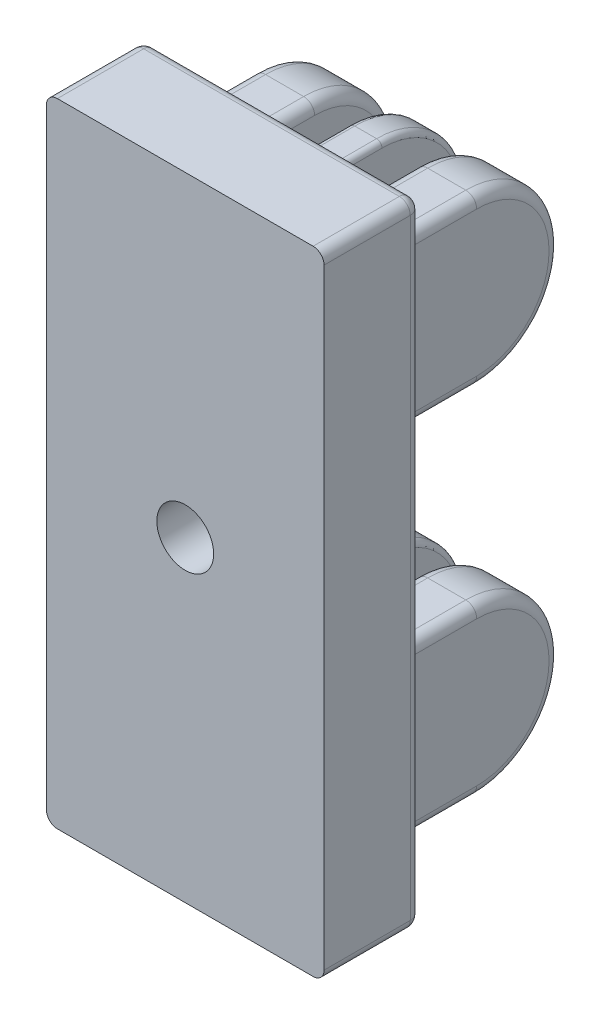
SolidWorks part; units mm, degrees
ref_plane "Front Plane" through (0, 0, 0) normal (0, 0, 1) x (1, 0, 0)
ref_plane "Top Plane" through (0, 0, 0) normal (0, 1, 0) x (1, 0, 0)
ref_plane "Right Plane" through (0, 0, 0) normal (1, 0, 0) x (0, 0, -1)
sketch "Sketch1" plane through (0, 0, 0) normal (0, 1, 0) x (1, 0, 0)
  line L1 (-12.7, -4.445) -> (12.7, -4.445)
  line L2 (-12.7, -4.445) -> (-12.7, 4.445)
  line L3 (-12.7, 4.445) -> (12.7, 4.445)
  line L4 (12.7, -4.445) -> (12.7, 4.445)
  line L5 (-12.7, -4.445) -> (12.7, 4.445) construction
  line L6 (-12.7, 4.445) -> (12.7, -4.445) construction
  point P0 (0, 0)
  dimension "D1" = 8.89
  dimension "D2" = 25.4
extrude "Boss-Extrude1" add sketch "Sketch1" along normal blind 38.1
sketch "Sketch2" plane through (0, 0, -4.445) normal (0, 0, -1) x (-1, 0, 0)
  line L1 (10.16, 5.08) -> (4.675, 5.08)
  line L2 (10.16, 5.08) -> (10.16, 20.32)
  line L3 (10.16, 20.32) -> (4.675, 20.32)
  line L4 (4.675, 5.08) -> (4.675, 20.32)
  line L5 (-10.16, 5.08) -> (-4.675, 5.08)
  line L6 (-10.16, 5.08) -> (-10.16, 20.32)
  line L7 (-10.16, 20.32) -> (-4.675, 20.32)
  line L8 (-4.675, 5.08) -> (-4.675, 20.32)
  line L9 (-1.5, 5.08) -> (1.5, 5.08)
  line L10 (-1.5, 5.08) -> (-1.5, 20.32)
  line L11 (-1.5, 20.32) -> (1.5, 20.32)
  line L12 (1.5, 5.08) -> (1.5, 20.32)
  line L13 (-1.5, 5.08) -> (1.5, 20.32) construction
  line L14 (-1.5, 20.32) -> (1.5, 5.08) construction
  line L15 (-12.7, 0) -> (12.7, 0) construction
  line L16 (12.7, 38.1) -> (12.7, 0) construction
  line L17 (-12.7, 38.1) -> (-12.7, 0) construction
  point P10 (0, 12.7)
  point P15 (-4.675, 12.7)
  dimension "D1" = 15.24
  dimension "D2" = 5.08
  dimension "D3" = 3.175
  dimension "D4" = 3.175
  dimension "D5" = 2.54
  dimension "D6" = 3
  dimension "D7" = 2.54
extrude "Boss-Extrude2" add sketch "Sketch2" along normal blind 15.24
sketch "Sketch3" plane through (-12.7, 0, 0) normal (-1, 0, 0) x (0, 0, 1)
  line L0 (-19.685, 5.08) -> (-4.445, 5.08) construction
  line L1 (-19.685, 5.08) -> (-19.685, 20.32) construction
  line L2 (-19.685, 20.32) -> (-4.445, 20.32) construction
  line L3 (-19.685, 5.08) -> (-12.065, 5.08)
  line L4 (-19.685, 20.32) -> (-12.065, 20.32)
  line L5 (-19.685, 5.08) -> (-19.685, 20.32)
  arc A0 (-12.065, 20.32) -> (-12.065, 5.08) centre (-12.065, 12.7) ccw
  point P0 (-12.065, 5.08)
  point P1 (-19.685, 12.7)
extrude "Cut-Extrude1" cut sketch "Sketch3" against normal through all
sketch "Sketch5" plane through (0, 0, -4.445) normal (0, 0, -1) x (-1, 0, 0)
  line L0 (12.7, 38.1) -> (12.7, 0) construction
  line L1 (-12.7, 38.1) -> (12.7, 38.1) construction
  circle A0 centre (0, 28.9364) radius 2.6
  point P0 (12.7, 19.05)
  point P1 (0, 38.1)
  dimension "D1" = 5.2
extrude "Cut-Extrude2" cut sketch "Sketch5" against normal through all
sketch "Sketch6" plane through (0, 0, -4.445) normal (0, 0, -1) x (-1, 0, 0)
  circle A0 centre (0, 28.9364) radius 5.15
  dimension "D1" = 10.3
extrude "Cut-Extrude3" cut sketch "Sketch6" against normal blind 5.08
fillet "Fillet9" radius 1 30 edges at (7.4175, 5.08, -4.445) (7.4175, 20.32, -4.445) (-7.4175, 5.08, -4.445) (-7.4175, 20.32, -4.445) (12.7, 19.05, -4.445) (0, 38.1, -4.445) (-12.7, 19.05, -4.445) (0, 0, -4.445) (-4.675, 5.08, -8.255) (-4.675, 12.7, -4.445) (-4.675, 20.32, -8.255) (-4.675, 12.7, -19.685) (4.675, 12.7, -4.445) (4.675, 5.08, -8.255) (4.675, 12.7, -19.685) (4.675, 20.32, -8.255) (10.16, 5.08, -8.255) (10.16, 12.7, -4.445) (10.16, 20.32, -8.255) (10.16, 12.7, -19.685) (-10.16, 12.7, -4.445) (-10.16, 5.08, -8.255) (-10.16, 12.7, -19.685) (-10.16, 20.32, -8.255) (12.7, 0, 0) (-12.7, 0, 0) (0, 5.08, -4.445) (1.5, 12.7, -4.445) (-1.5, 12.7, -4.445) (0, 20.32, -4.445)
fillet "Fillet10" radius 1 1 edges at (-5.15, 28.9364, -4.445)
fillet "Fillet11" radius 0.5 10 edges at (1.7929, 4.7871, -4.7379) (1.7929, 20.6129, -4.7379) (-1.7929, 20.6129, -4.7379) (-1.5, 20.32, -8.755) (-1.5, 12.7, -19.685) (-1.7929, 4.7871, -4.7379) (1.5, 12.7, -19.685) (1.5, 5.08, -8.755) (1.5, 20.32, -8.755) (-1.5, 5.08, -8.755)
sketch "Sketch7" plane through (0, 0, -4.445) normal (0, 0, -1) x (-1, 0, 0)
  line L0 (-12.7, 28.9364) -> (12.7, 28.9364)
  line L1 (-12.7, 1) -> (-12.7, 38.1) construction
  line L2 (-12.7, 38.1) -> (12.7, 38.1) construction
  line L3 (12.7, 38.1) -> (12.7, 1) construction
  line L4 (-12.7, 28.9364) -> (-12.7, 38.1)
  line L5 (-12.7, 38.1) -> (12.7, 38.1)
  line L6 (12.7, 38.1) -> (12.7, 28.9364)
  point P4 (0, 28.9364)
extrude "Cut-Extrude4" cut sketch "Sketch7" against normal through all
mirror "Mirror1" about plane through (12.7, 28.9364, 4.445) normal (0, -1, 0)
